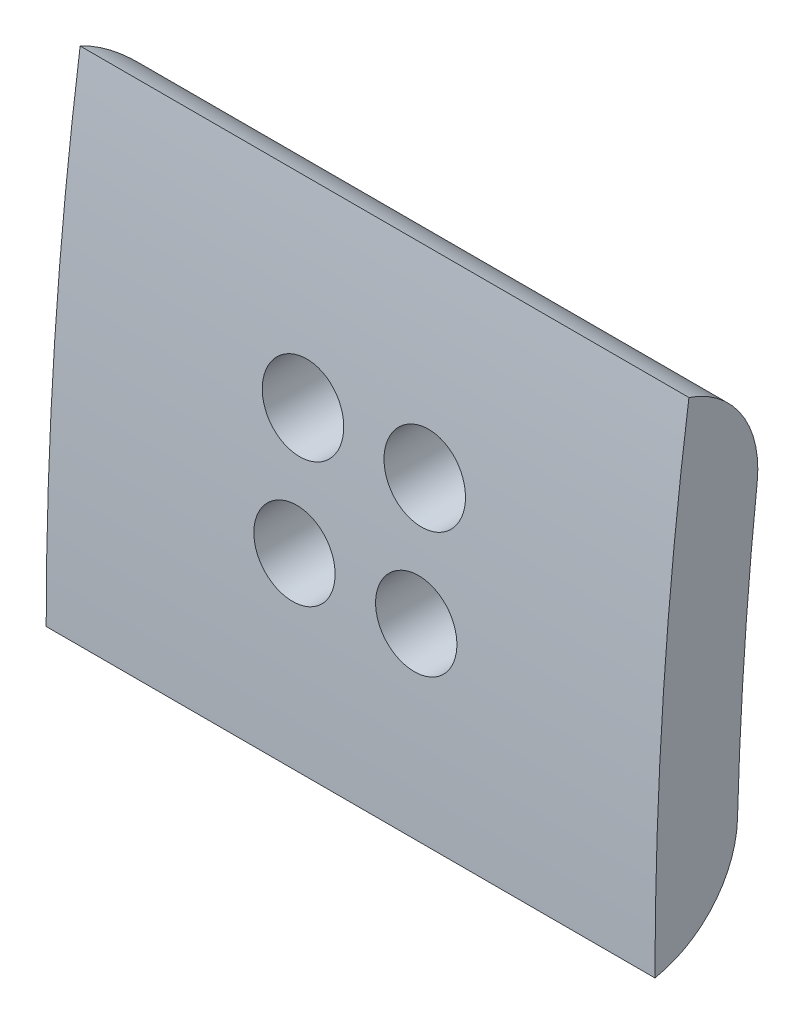
SolidWorks part; units mm, degrees
ref_plane "Alzado" through (0, 0, 0) normal (0, 0, 1) x (1, 0, 0)
ref_plane "Planta" through (0, 0, 0) normal (0, 1, 0) x (1, 0, 0)
ref_plane "Vista lateral" through (0, 0, 0) normal (1, 0, 0) x (0, 0, -1)
sketch "Croquis1" plane through (0, 0, 0) normal (1, 0, 0) x (0, 0, -1)
  line L0 (-172, 0) -> (-168, 0)
  line L1 (-170.3261, 23.9378) -> (-166.365, 23.3811)
  arc A0 (-170.3261, 23.9378) -> (-172, 0) centre (0, 0) ccw
  arc A1 (-166.365, 23.3811) -> (-168, 0) centre (0, 0) ccw
  dimension "D1" = 344
  dimension "D2" = 4
  dimension "D3" = 8
extrude "Saliente-Extruir1" add sketch "Croquis1" along normal blind 30
fillet "Redondeo1" radius 5 3 edges at (15, 0, 168) (0, 11.7191, 167.5908) (15, 23.3811, 166.365)
ref_plane "Plano1" through (0, 0, 160.05) normal (0, 0, 1) x (1, 0, 0)
sketch "Croquis2" plane through (0, 0, 160.05) normal (0, 0, 1) x (1, 0, 0)
  line L0 (18, 15) -> (12, 15) construction
  line L1 (12, 15) -> (15, 15) construction
  line L2 (15, 15) -> (15, 9) construction
  line L3 (15, 9) -> (18, 9) construction
  line L4 (18, 9) -> (12, 9) construction
  line L5 (12, 9) -> (15, 9) construction
  line L6 (15, 9) -> (15, 12) construction
  line L7 (0, 23.9378) -> (0, 0) construction
  line L10 (30, 0) -> (0, 0) construction
  circle A0 centre (18, 15) radius 2
  circle A1 centre (12, 15) radius 2
  circle A2 centre (18, 9) radius 2
  circle A3 centre (12, 9) radius 2
  dimension "D1" = 4
  dimension "D2" = 6
  dimension "D3" = 6
  dimension "D4" = 6
  dimension "D6" = 6
  dimension "D5" = 15
  dimension "D7" = 12
extrude "Cortar-Extruir1" cut sketch "Croquis2" along normal through all
